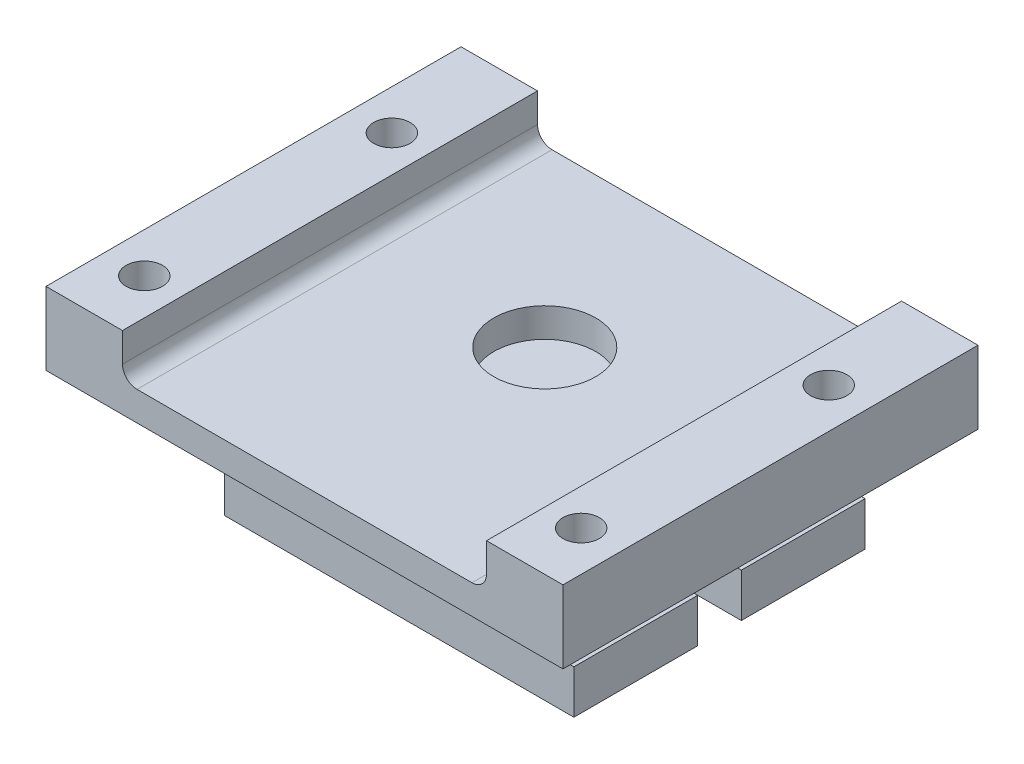
SolidWorks part; units mm, degrees
ref_plane "Front Plane" through (0, 0, 0) normal (0, 0, 1) x (1, 0, 0)
ref_plane "Top Plane" through (0, 0, 0) normal (0, 1, 0) x (1, 0, 0)
ref_plane "Right Plane" through (0, 0, 0) normal (1, 0, 0) x (0, 0, -1)
sketch "Sketch1" plane through (0, 0, 0) normal (0, 1, 0) x (1, 0, 0)
  line L0 (15, 4.5) -> (-15, 4.5) construction
  line L5 (-17.75, 12) -> (17.75, 12)
  line L6 (-17.75, 12) -> (-17.75, -16.5)
  line L7 (-17.75, -16.5) -> (17.75, -16.5)
  line L8 (17.75, 12) -> (17.75, -16.5)
  line L9 (-17.75, 12) -> (17.75, -16.5) construction
  line L10 (-17.75, -16.5) -> (17.75, 12) construction
  circle A6 centre (-15, 4.5) radius 1.25
  circle A7 centre (15, 4.5) radius 1.25
  circle A8 centre (-15, -12.5) radius 1.25
  circle A9 centre (15, -12.5) radius 1.25
  point P0 (0, -2.25)
  point P14 (0, 4.5)
  dimension "D4" = 12.5
  dimension "D5" = 2.5
  dimension "D1" = 35.5
  dimension "D2" = 4.5
  dimension "D3" = 12
  dimension "D6" = 30
  dimension "D7" = 4
extrude "Boss-Extrude1" add sketch "Sketch1" along normal blind 5
sketch "Sketch2" plane through (0, 5, 0) normal (0, 1, 0) x (1, 0, 0)
  line L0 (-17.75, -16.5) -> (17.75, -16.5) construction
  line L1 (12.5, -16.5) -> (-12.5, -16.5)
  line L2 (12.5, -16.5) -> (12.5, 12)
  line L3 (12.5, 12) -> (-12.5, 12)
  line L4 (-12.5, -16.5) -> (-12.5, 12)
  line L5 (17.75, 12) -> (-17.75, 12) construction
  circle A0 centre (0, 0) radius 3.5
  point P6 (0, 12)
  dimension "D2" = 7
  dimension "D1" = 25
extrude "Cut-Extrude1" cut sketch "Sketch2" against normal blind 3
sketch "Sketch3" plane through (0, 5, 0) normal (0, 1, 0) x (1, 0, 0)
  circle A1 centre (0, 0) radius 3.5
  circle A2 centre (0, 0) radius 3.5
  dimension "D1" = 0
extrude "Cut-Extrude2" cut sketch "Sketch3" against normal through all both and the other way through all
fillet "Fillet1" radius 1 2 edges at (12.5, 2, 2.25) (-12.5, 2, 2.25)
sketch "Sketch4" plane through (0, 0, 0) normal (0, -1, 0) x (1, 0, 0)
  line L1 (-15, 10) -> (15, 10)
  line L2 (-15, 10) -> (-15, -10)
  line L3 (-15, -10) -> (15, -10)
  line L4 (15, 10) -> (15, -10)
  line L5 (-15, 10) -> (15, -10) construction
  line L6 (-15, -10) -> (15, 10) construction
  point P0 (0, 0)
  circle M5 centre (0, 0) radius 3.5
  circle M10 centre (-15, -4.5) radius 1.25
  circle M11 centre (15, -4.5) radius 1.25
  dimension "D1" = 30
  dimension "D2" = 20
extrude "Boss-Extrude5" add sketch "Sketch4" along normal blind 9 contours L4 L1 L2 L3 M10 M11 M5 | M5 | L2 L1 L4 L3 region at (0, 0, 9.6394) region at (0, 0, 0)
sketch "Sketch7" plane through (0, 0, -10) normal (0, 0, -1) x (-1, 0, 0)
  line L0 (-12, -9) -> (-12, -6)
  line L1 (-12, -6) -> (-9, -6)
  line L2 (-9, -6) -> (-9, 0)
  line L3 (-9, 0) -> (9, 0)
  line L4 (15, 0) -> (-15, 0)
  line L5 (-15, 0) -> (-15, -9)
  line L6 (-15, -9) -> (15, -9)
  line L7 (15, -9) -> (15, 0)
  line L8 (15, 0) -> (-15, 0)
  line L9 (-15, 0) -> (-15, -9)
  line L10 (-15, -9) -> (15, -9)
  line L11 (15, -9) -> (15, 0)
  line L12 (9, 0) -> (9, -6)
  line L13 (9, -6) -> (12, -6)
  line L14 (12, -6) -> (12, -9)
  point P12 (8.1833, -5.5527)
  line M9 (15, 0) -> (-15, 0)
  line M10 (-15, 0) -> (-15, -9)
  line M11 (-15, -9) -> (15, -9)
  line M12 (15, -9) -> (15, 0)
  dimension "D2" = 3
  dimension "D3" = 3
  dimension "D4" = 3
  dimension "D5" = 3
  dimension "D6" = 3
  dimension "D1" = 0
extrude "Cut-Extrude7" cut sketch "Sketch7" against normal through all both contours L13 L14 L10 L12 M12 M9 | L1 L2 L0 M9 M10 M11 region at (12.3, -3.9, -10) region at (-12.3, -3.9, -10)
sketch "Sketch8" plane through (-12, 0, 0) normal (-1, 0, 0) x (0, 0, 1)
  line L0 (10, -9) -> (-10, -9) construction
  line L1 (1.5, -9) -> (-1.5, -9)
  line L2 (1.5, -9) -> (1.5, -6)
  line L3 (1.5, -6) -> (-1.5, -6)
  line L4 (-1.5, -9) -> (-1.5, -6)
  line L5 (10, -6) -> (-10, -6) construction
  point P9 (0, -6)
  dimension "D1" = 3
extrude "Cut-Extrude8" cut sketch "Sketch8" against normal through all both
fillet "Fillet2" radius 2 4 edges at (9, 0, 0) (-9, 0, 0) (0, -6, -1.5) (0, -6, 1.5)
